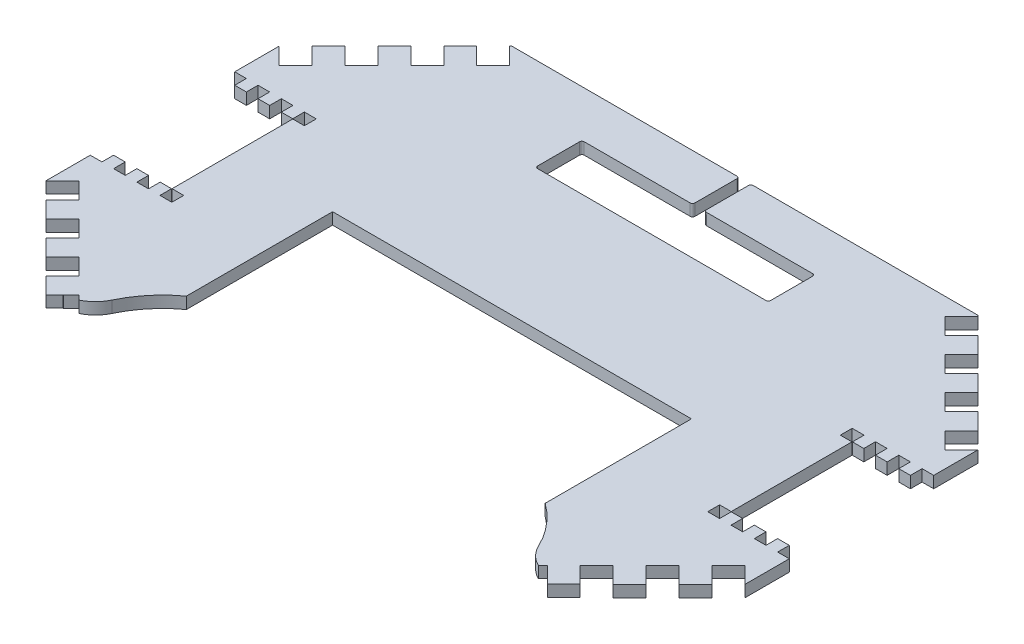
SolidWorks part; units mm, degrees
material "Balsa"
ref_plane "Plan de face" through (0, 0, 0) normal (0, 0, 1) x (1, 0, 0)
ref_plane "Plan de dessus" through (0, 0, 0) normal (0, 1, 0) x (1, 0, 0)
ref_plane "Plan de droite" through (0, 0, 0) normal (1, 0, 0) x (0, 0, -1)
sketch "Esquisse1" plane through (0, 0, 0) normal (0, 1, 0) x (1, 0, 0)
  line L1 (-150, 100) -> (150, 100)
  line L2 (-150, 100) -> (-150, -100)
  line L3 (-150, -100) -> (150, -100)
  line L4 (150, 100) -> (150, -100)
  dimension "D1" = 300
  dimension "D2" = 200
  dimension "D3" = 150
  dimension "D4" = 100
extrude "Boss.-Extru.1" add sketch "Esquisse1" along normal blind 5
sketch "Esquisse2" plane through (0, 5, 0) normal (0, 1, 0) x (1, 0, 0)
  line L0 (-100, 100) -> (-150, 50)
  line L1 (150, 100) -> (-150, 100) construction
  line L2 (-150, 100) -> (-150, -100) construction
  line L3 (-150, 50) -> (-150, 100)
  line L4 (-150, 100) -> (-100, 100)
  line L5 (150, 100) -> (150, 50)
  line L6 (150, -100) -> (150, 100) construction
  line L7 (150, 50) -> (100, 100)
  line L8 (100, 100) -> (150, 100)
  line L9 (150, -100) -> (150, -50)
  line L10 (150, -50) -> (100, -100)
  line L11 (-150, -100) -> (150, -100) construction
  line L12 (100, -100) -> (150, -100)
  line L13 (-100, -100) -> (-150, -100)
  line L14 (-150, -100) -> (-150, -50)
  line L15 (-150, -50) -> (-100, -100)
  dimension "D1" = 50
  dimension "D2" = 50
  dimension "D3" = 50
  dimension "D4" = 50
  dimension "D5" = 50
  dimension "D6" = 50
  dimension "D7" = 50
  dimension "D8" = 50
extrude "Enlèv. mat.-Extru.1" cut sketch "Esquisse2" against normal blind 10
sketch "Esquisse10" plane through (0, 5, 0) normal (0, 1, 0) x (1, 0, 0)
  line L0 (-100, -100) -> (100, -100) construction
  circle A0 centre (-50, -100) radius 46
  dimension "D2" = 92
  dimension "D1" = 50
extrude "Enlèv. mat.-Extru.9" cut sketch "Esquisse10" against normal blind 10
mirror "Symétrie2" about plane through (0, 0, 0) normal (1, 0, 0) of "Enlèv. mat.-Extru.9"
fillet "Congé2" radius 15 3 edges at (96, 2.5, 100) (-4, 2.5, 100) (-96, 2.5, 100)
fillet "Congé3" radius 15 3 edges at (4, 2.5, 100) (100, 2.5, 100) (-100, 2.5, 100)
sketch "Esquisse11" plane through (0, 5, 0) normal (0, 1, 0) x (1, 0, 0)
  line L0 (-150, 50) -> (-142.9289, 57.0711)
  line L1 (-150, 50) -> (-142.9289, 42.9289)
  line L2 (-142.9289, 57.0711) -> (-135.8579, 50)
  line L3 (-142.9289, 42.9289) -> (-135.8579, 50)
  line L4 (-150, 50) -> (-100, 100) construction
  dimension "D1" = 10
  dimension "D2" = 10
extrude "Enlèv. mat.-Extru.10" cut sketch "Esquisse11" against normal blind 10
pattern_linear "Répétition linéaire1" count 4 spacing 20 along (0.7071, 0, -0.7071) of "Enlèv. mat.-Extru.10"
mirror "Symétrie3" about plane through (0, 0, 0) normal (0, 0, 1) of "Répétition linéaire1", "Enlèv. mat.-Extru.10"
mirror "Symétrie4" about plane through (0, 0, 0) normal (1, 0, 0) of "Symétrie3", "Enlèv. mat.-Extru.10", "Répétition linéaire1"
sketch "Esquisse16" plane through (0, 5, 0) normal (0, 1, 0) x (1, 0, 0)
  line L1 (77, -100) -> (-77, -100)
  line L2 (77, -100) -> (77, 0)
  line L3 (77, 0) -> (-77, 0)
  line L4 (-77, -100) -> (-77, 0)
  dimension "D1" = 154
  dimension "D2" = 77
  dimension "D3" = 0
  dimension "D4" = 100
extrude "Enlèv. mat.-Extru.15" cut sketch "Esquisse16" against normal blind 10
sketch "Esquisse24" plane through (0, 5, 0) normal (0, 1, 0) x (1, 0, 0)
  line L0 (-150, 50) -> (-150, -50) construction
  line L1 (-150, 26) -> (-120, 26)
  line L2 (-150, 26) -> (-150, -26)
  line L3 (-150, -26) -> (-120, -26)
  line L4 (-120, 26) -> (-120, -26)
  line L5 (0, 35.7174) -> (0, -32.4568) construction
  line L6 (120, 26) -> (120, -26)
  line L7 (150, -26) -> (120, -26)
  line L8 (150, 26) -> (150, -26)
  line L9 (150, 26) -> (120, 26)
  dimension "D1" = 52
  dimension "D2" = 30
  dimension "D3" = 24
extrude "Enlèv. mat.-Extru.18" cut sketch "Esquisse24" against normal blind 10
sketch "Esquisse25" plane through (0, 5, 0) normal (0, 1, 0) x (1, 0, 0)
  line L1 (-120, 26) -> (-150, 26) construction
  line L2 (-145, 31) -> (-150.1, 31)
  line L3 (-145, 31) -> (-145, 25.9)
  line L4 (-145, 25.9) -> (-150.1, 25.9)
  line L6 (-150.1, 31) -> (-150.1, 25.9)
  line L7 (-150, 50) -> (-150, 26) construction
  line L8 (-130, 31) -> (-125, 31)
  line L9 (-140, 31) -> (-135, 31)
  line L10 (-140, 31) -> (-140, 25.9)
  line L11 (-140, 25.9) -> (-135, 25.9)
  line L12 (-135, 31) -> (-135, 25.9)
  line L13 (-125, 31) -> (-125, 25.9)
  line L14 (-130, 25.9) -> (-125, 25.9)
  line L15 (-130, 31) -> (-130, 25.9)
  line L16 (-120, 0) -> (0, 0) construction
  line L17 (-120.1, 31) -> (-115, 31)
  line L18 (-120.1, 31) -> (-120.1, 25.9)
  line L19 (-120.1, 25.9) -> (-115, 25.9)
  line L20 (-115, 31) -> (-115, 25.9)
  line L21 (-120, -26) -> (-120, 26) construction
  line L22 (77, 0) -> (-77, 0) construction
  line L24 (0, 0) -> (0, -24.7536) construction
  line L33 (-115, -31) -> (-115, -25.9)
  line L34 (-120.1, -25.9) -> (-115, -25.9)
  line L35 (-120.1, -31) -> (-120.1, -25.9)
  line L36 (-120.1, -31) -> (-115, -31)
  line L37 (-130, -31) -> (-130, -25.9)
  line L38 (-130, -25.9) -> (-125, -25.9)
  line L39 (-125, -31) -> (-125, -25.9)
  line L40 (-135, -31) -> (-135, -25.9)
  line L41 (-140, -25.9) -> (-135, -25.9)
  line L42 (-140, -31) -> (-140, -25.9)
  line L43 (-140, -31) -> (-135, -31)
  line L44 (-130, -31) -> (-125, -31)
  line L45 (-150.1, -31) -> (-150.1, -25.9)
  line L46 (-145, -25.9) -> (-150.1, -25.9)
  line L47 (-145, -31) -> (-145, -25.9)
  line L48 (-145, -31) -> (-150.1, -31)
  line L49 (145, -31) -> (150.1, -31)
  line L50 (145, -31) -> (145, -25.9)
  line L51 (145, -25.9) -> (150.1, -25.9)
  line L52 (150.1, -31) -> (150.1, -25.9)
  line L53 (130, -31) -> (125, -31)
  line L54 (140, -31) -> (135, -31)
  line L55 (140, -31) -> (140, -25.9)
  line L56 (140, -25.9) -> (135, -25.9)
  line L57 (135, -31) -> (135, -25.9)
  line L58 (125, -31) -> (125, -25.9)
  line L59 (130, -25.9) -> (125, -25.9)
  line L60 (130, -31) -> (130, -25.9)
  line L61 (120.1, -31) -> (115, -31)
  line L62 (120.1, -31) -> (120.1, -25.9)
  line L63 (120.1, -25.9) -> (115, -25.9)
  line L64 (115, -31) -> (115, -25.9)
  line L73 (115, 31) -> (115, 25.9)
  line L74 (120.1, 25.9) -> (115, 25.9)
  line L75 (120.1, 31) -> (120.1, 25.9)
  line L76 (120.1, 31) -> (115, 31)
  line L77 (130, 31) -> (130, 25.9)
  line L78 (130, 25.9) -> (125, 25.9)
  line L79 (125, 31) -> (125, 25.9)
  line L80 (135, 31) -> (135, 25.9)
  line L81 (140, 25.9) -> (135, 25.9)
  line L82 (140, 31) -> (140, 25.9)
  line L83 (140, 31) -> (135, 31)
  line L84 (130, 31) -> (125, 31)
  line L85 (150.1, 31) -> (150.1, 25.9)
  line L86 (145, 25.9) -> (150.1, 25.9)
  line L87 (145, 31) -> (145, 25.9)
  line L88 (145, 31) -> (150.1, 31)
  dimension "D1" = 5.1
  dimension "D2" = 5.1
  dimension "D4" = 0.1
  dimension "D5" = 5
  dimension "D3" = 5
  dimension "D6" = 5.1
  dimension "D7" = 5
  dimension "D8" = 0.1
  dimension "D10" = 5.1
  dimension "D9" = 5.1
  dimension "D11" = 4.9
  dimension "D12" = 5
  dimension "D13" = 5
  dimension "D14" = 5.1
extrude "Enlèv. mat.-Extru.21" cut sketch "Esquisse25" against normal blind 10
sketch "Esquisse26" plane through (0, 5, 0) normal (0, 1, 0) x (1, 0, 0)
  line L0 (100, 100) -> (-100, 100) construction
  line L1 (-50, 80) -> (50, 80)
  line L2 (-50, 80) -> (-50, 60)
  line L3 (-50, 60) -> (50, 60)
  line L4 (50, 80) -> (50, 60)
  dimension "D1" = 20
  dimension "D2" = 100
  dimension "D3" = 20
  dimension "D4" = 50
extrude "Enlèv. mat.-Extru.22" cut sketch "Esquisse26" against normal blind 10
sketch "Esquisse27" plane through (0, 5, 0) normal (0, 1, 0) x (1, 0, 0)
  line L0 (50, 80) -> (-50, 80) construction
  line L1 (2.5, 80) -> (-2.5, 80)
  line L2 (2.5, 80) -> (2.5, 100)
  line L3 (2.5, 100) -> (-2.5, 100)
  line L4 (-2.5, 80) -> (-2.5, 100)
  line L5 (100, 100) -> (-100, 100) construction
  dimension "D1" = 97.5
  dimension "D2" = 97.5
extrude "Enlèv. mat.-Extru.23" cut sketch "Esquisse27" against normal blind 10
fillet "Congé4" radius 1 8 edges at (-50, 2.5, -80) (-50, 2.5, -60) (50, 2.5, -80) (-2.5, 2.5, -80) (2.5, 2.5, -80) (-2.5, 2.5, -100) (2.5, 2.5, -100) (50, 2.5, -60)
sketch "Esquisse28" plane through (0, 5, 0) normal (0, 1, 0) x (1, 0, 0)
  line L0 (107.5736, -78.2843) -> (114.5958, -85.3065)
  line L1 (107.5736, -78.2843) -> (100.5513, -85.3065)
  line L2 (100.5513, -85.3065) -> (107.5736, -92.3288)
  line L3 (107.5736, -92.3288) -> (114.5958, -85.3065)
  line L4 (0, 33.3693) -> (0, 0) construction
  line L5 (-107.5736, -92.3288) -> (-114.5958, -85.3065)
  line L6 (-100.5513, -85.3065) -> (-107.5736, -92.3288)
  line L7 (-107.5736, -78.2843) -> (-100.5513, -85.3065)
  line L8 (-107.5736, -78.2843) -> (-114.5958, -85.3065)
extrude "Boss.-Extru.2" add sketch "Esquisse28" against normal blind 5
